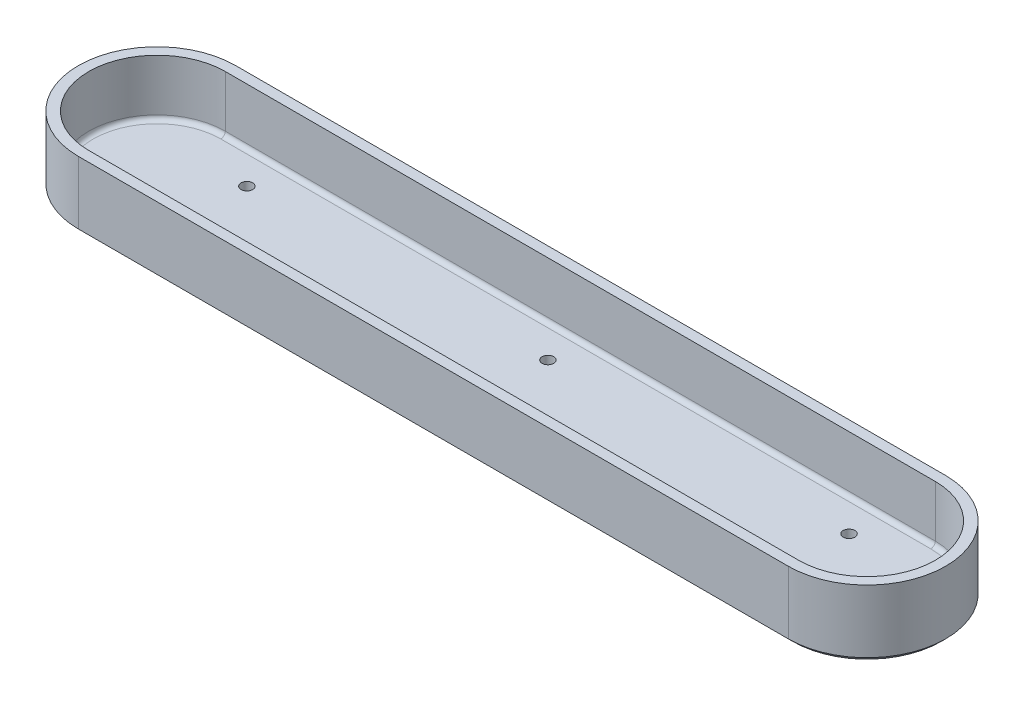
SolidWorks part; units mm, degrees
material "PLA"
ref_plane "Front Plane" through (0, 0, 0) normal (0, 0, 1) x (1, 0, 0)
ref_plane "Top Plane" through (0, 0, 0) normal (0, 1, 0) x (1, 0, 0)
ref_plane "Right Plane" through (0, 0, 0) normal (1, 0, 0) x (0, 0, -1)
sketch "Sketch1" plane through (0, 0, 0) normal (0, 1, 0) x (1, 0, 0)
  line L0 (-100.33, 0) -> (100.33, 0) construction
  line L1 (0, -55.9739) -> (0, 55.9739) construction
  line L2 (-100.33, 19.304) -> (100.33, 19.304)
  line L3 (-100.33, -19.304) -> (100.33, -19.304)
  arc A0 (-100.33, 19.304) -> (-100.33, -19.304) centre (-100.33, 0) ccw
  arc A1 (100.33, 19.304) -> (100.33, -19.304) centre (100.33, 0) cw
  circle A2 centre (-100.33, 0) radius 19.05 construction
  point P4 (0, 0)
  point P10 (0, 0)
  dimension "D2" = 0.254
  dimension "D3" = 38.1
  dimension "D1" = 200.66
extrude "MainBlock" add sketch "Sketch1" along normal blind 3.175
sketch "Sketch2" plane through (0, 0, 0) normal (0, -1, 0) x (1, 0, 0)
  line L0 (0, 0) -> (0, 50000) construction
  line L1 (-100.33, 22.225) -> (100.33, 22.225)
  line L2 (-100.33, -19.304) -> (100.33, -19.304)
  line L3 (100.33, 19.304) -> (-100.33, 19.304)
  line L5 (100.33, 19.304) -> (-100.33, 19.304)
  line L6 (-95.25, 0) -> (49904.75, 0) construction
  line L7 (100.33, -19.304) -> (-100.33, -19.304)
  line L8 (-100.33, -22.225) -> (100.33, -22.225)
  arc A0 (-100.33, 22.225) -> (-100.33, -22.225) centre (-100.33, 0) ccw
  arc A1 (100.33, 19.304) -> (100.33, -19.304) centre (100.33, 0) cw
  arc A2 (-100.33, 19.304) -> (-100.33, -19.304) centre (-100.33, 0) ccw
  arc A3 (100.33, -19.304) -> (100.33, 19.304) centre (100.33, 0) ccw
  arc A4 (-100.33, 19.304) -> (-100.33, -19.304) centre (-100.33, 0) ccw
  arc A6 (100.33, 22.225) -> (100.33, -22.225) centre (100.33, 0) cw
  point P0 (0, 19.304)
  point P15 (0, 22.225)
  point P16 (0, -19.304)
  point P19 (0, -22.225)
  dimension "D2" = 2.921
  dimension "2.1" = 44.45
  dimension "D1" = 0
extrude "Boss-Extrude1" add sketch "Sketch2" against normal blind 19.05
sketch "Sketch3" plane through (0, 0, 0) normal (0, -1, 0) x (1, 0, 0)
  line L0 (0, 0) -> (50000, 0) construction
  line L1 (0, 0) -> (0, 50000) construction
  line L2 (-100.33, 0.9216) -> (-100.33, 50000.9216) construction
  arc A0 (-100.33, 22.225) -> (-100.33, -22.225) centre (-100.33, 0) ccw construction
  arc A1 (-100.33, 22.225) -> (-100.33, -22.225) centre (-100.33, 0) ccw construction
  circle A2 centre (0, 10.16) radius 1.651
  circle A3 centre (-85.09, 10.16) radius 1.651
  circle A4 centre (85.09, 10.16) radius 1.651
  circle A5 centre (85.09, -10.16) radius 1.651
  circle A6 centre (-85.09, -10.16) radius 1.651
  circle A7 centre (0, -10.16) radius 1.651
  dimension "D1" = 3.302
  dimension "D4" = 3.302
  dimension "D2" = 10.16
  dimension "D3" = 10.16
  dimension "D5" = 15.24
extrude "Mount-Holes" cut sketch "Sketch3" against normal through all
fillet "Fillet1" radius 1.27 4 edges at (119.634, 3.175, 0) (0, 3.175, 19.304) (-119.634, 3.175, 0) (0, 3.175, -19.304)
chamfer "Chamfer1" distance 1.27 angle 45 4 edges at (0, 0, 22.225) (-122.555, 0, 0) (122.555, 0, 0) (0, 0, -22.225)
equation "\"D4@Sketch3\"=\"D1@Sketch3\""
